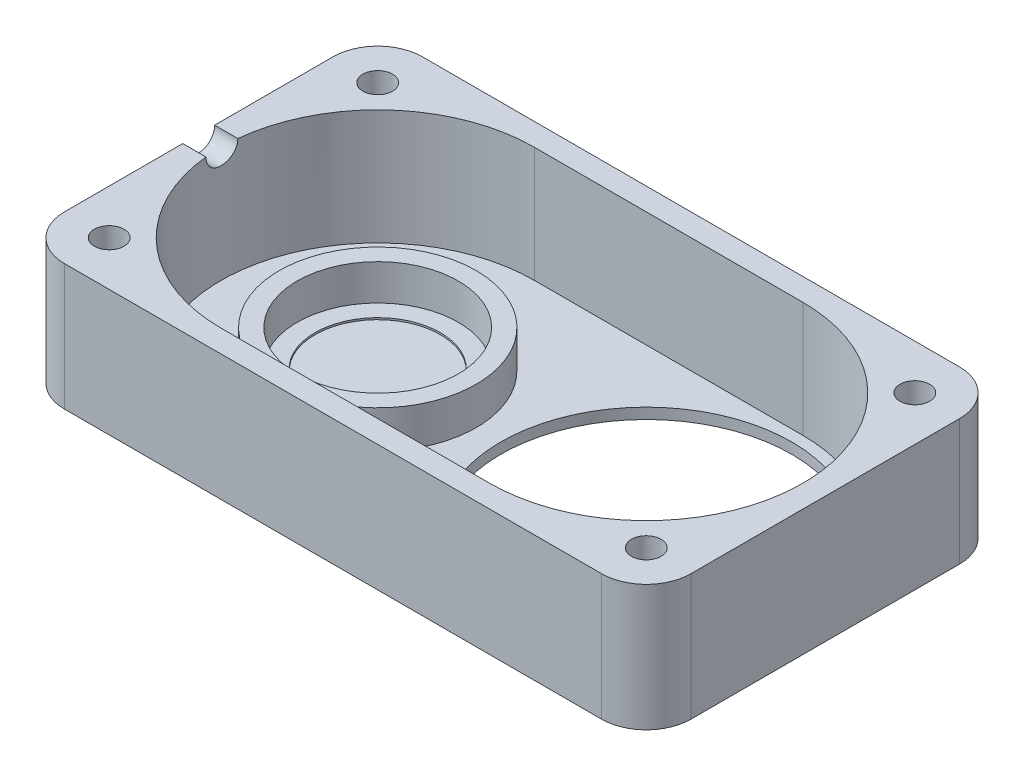
SolidWorks part; units mm, degrees
ref_plane "Front Plane" through (0, 0, 0) normal (0, 0, 1) x (1, 0, 0)
ref_plane "Top Plane" through (0, 0, 0) normal (0, 1, 0) x (1, 0, 0)
ref_plane "Right Plane" through (0, 0, 0) normal (1, 0, 0) x (0, 0, -1)
sketch "Sketch1" plane through (0, 0, 0) normal (0, 1, 0) x (1, 0, 0)
  line L0 (38.1, 19.05) -> (38.1, 25.4) construction
  line L1 (-19.05, -25.4) -> (57.15, -25.4)
  line L2 (-25.4, -19.05) -> (-25.4, 19.05)
  line L3 (-19.05, 25.4) -> (57.15, 25.4)
  line L4 (63.5, -19.05) -> (63.5, 19.05)
  line L5 (-25.4, -25.4) -> (63.5, 25.4) construction
  line L6 (-25.4, 25.4) -> (63.5, -25.4) construction
  line L7 (57.15, 0) -> (63.5, 0) construction
  line L9 (-7.62, -11.176) -> (7.62, -11.176) construction
  line L10 (-7.62, -11.176) -> (-7.62, 11.176) construction
  line L11 (-7.62, 11.176) -> (7.62, 11.176) construction
  line L12 (7.62, -11.176) -> (7.62, 11.176) construction
  line L13 (-7.62, -11.176) -> (7.62, 11.176) construction
  line L14 (-7.62, 11.176) -> (7.62, -11.176) construction
  circle A0 centre (0, 0) radius 19.05 construction
  circle A1 centre (38.1, 0) radius 19.05 construction
  circle A2 centre (38.1, 0) radius 12.7 construction
  circle A3 centre (38.1, 0) radius 20.6375
  arc A4 (-25.4, 19.05) -> (-19.05, 25.4) centre (-19.05, 19.05) cw
  arc A5 (-19.05, -25.4) -> (-25.4, -19.05) centre (-19.05, -19.05) cw
  arc A6 (57.15, -25.4) -> (63.5, -19.05) centre (57.15, -19.05) ccw
  arc A7 (57.15, 25.4) -> (63.5, 19.05) centre (57.15, 19.05) cw
  circle A8 centre (-19.05, 19.05) radius 2.1
  circle A9 centre (-19.05, -19.05) radius 2.1
  circle A10 centre (57.15, -19.05) radius 2.1
  circle A11 centre (57.15, 19.05) radius 2.1
  point P6 (19.05, 0)
  dimension "D1" = 38.1
  dimension "D2" = 38.1
  dimension "D3" = 50.8
  dimension "D7" = 25.4
  dimension "D8" = 41.275
  dimension "D9" = 6.35
  dimension "D10" = 4.2
  dimension "D4" = 88.9
  dimension "D5" = 15.24
  dimension "D6" = 22.352
extrude "Boss-Extrude1" add sketch "Sketch1" along normal blind 17.8791
sketch "Sketch2" plane through (0, 17.8791, 0) normal (0, 1, 0) x (1, 0, 0)
  line L0 (0, 22.225) -> (38.1, 22.225)
  line L1 (38.1, -22.225) -> (0, -22.225)
  arc A0 (0, 22.225) -> (0, -22.225) centre (0, 0) ccw
  arc A1 (38.1, -22.225) -> (38.1, 22.225) centre (38.1, 0) ccw
  dimension "D1" = 44.45
extrude "Cut-Extrude1" cut sketch "Sketch2" against normal offset from surface (16.3551 mm away) 1.524 up to face at (57.15, 0, 21.15)
sketch "Sketch3" plane through (0, 1.524, 0) normal (0, 1, 0) x (1, 0, 0)
  circle A0 centre (0, 0) radius 13.97
  circle A1 centre (0, 0) radius 8.89
  dimension "D1" = 27.94
  dimension "D2" = 17.78
extrude "Boss-Extrude2" add sketch "Sketch3" along normal blind 0.254
sketch "Sketch4" plane through (0, 1.778, 0) normal (0, 1, 0) x (1, 0, 0)
  circle A0 centre (0, 0) radius 11.43
  circle A1 centre (0, 0) radius 13.97 construction
  circle A2 centre (0, 0) radius 13.97
  dimension "D1" = 22.86
extrude "Boss-Extrude3" add sketch "Sketch4" along normal blind 5.08
sketch "Sketch6" plane through (-25.4, 0, 0) normal (-1, 0, 0) x (0, 0, 1)
  line L0 (-19.05, 17.8791) -> (19.05, 17.8791) construction
  circle A0 centre (0, 17.8791) radius 2.2606
  dimension "D1" = 4.5212
extrude "Cut-Extrude2" cut sketch "Sketch6" against normal up to next
sketch "Sketch7" plane through (0, 0, 0) normal (0, -1, 0) x (1, 0, 0)
  circle A0 centre (-19.05, 19.05) radius 3.75
  circle A1 centre (-19.05, -19.05) radius 3.75
  circle A2 centre (57.15, -19.05) radius 3.75
  circle A3 centre (57.15, 19.05) radius 3.75
  dimension "D1" = 7.5
extrude "Cut-Extrude3" cut sketch "Sketch7" against normal blind 4.5
sketch "Sketch8" plane through (0, 0, 0) normal (0, -1, 0) x (1, 0, 0)
  line L0 (20.4837, 10.7504) -> (14.9909, 15.9577)
  line L1 (14.9909, 15.9577) -> (20.9323, 22.225)
  line L2 (20.9323, 22.225) -> (26.4252, 17.0178)
  line L3 (17.9616, 19.0913) -> (38.1, 0) construction
  line L4 (0, 22.225) -> (38.1, 22.225) construction
  circle A0 centre (38.1, 0) radius 20.6375 construction
  arc A1 (26.4252, 17.0178) -> (20.4837, 10.7504) centre (38.1, 0) ccw
  point P8 (23.1229, 14.1984)
  dimension "D1" = 8.636
  dimension "D2" = 7.112
extrude "Cut-Extrude4" cut sketch "Sketch8" against normal through all
